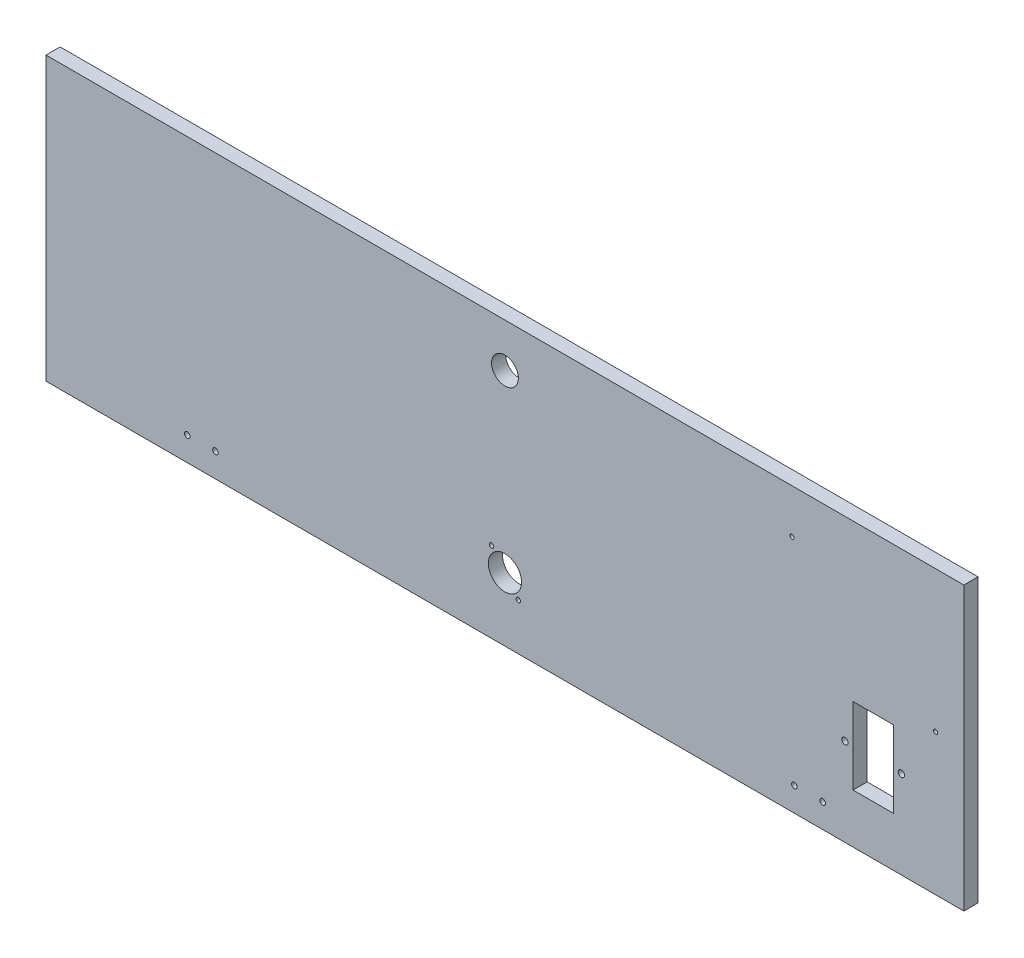
SolidWorks part; units mm, degrees
ref_plane "Plan de face" through (0, 0, 0) normal (0, 0, 1) x (1, 0, 0)
ref_plane "Plan de dessus" through (0, 0, 0) normal (0, 1, 0) x (1, 0, 0)
ref_plane "Plan de droite" through (0, 0, 0) normal (1, 0, 0) x (0, 0, -1)
sketch "Esquisse1" plane through (0, 0, 0) normal (0, 0, 1) x (1, 0, 0)
  line L1 (0, 0) -> (650, 0)
  line L2 (0, 0) -> (0, 200)
  line L3 (0, 200) -> (650, 200)
  line L4 (650, 0) -> (650, 200)
  dimension "D1" = 200
  dimension "D2" = 650
extrude "Boss.-Extru.1" add sketch "Esquisse1" along normal blind 10
sketch "Esquisse2" plane through (0, 0, 10) normal (0, 0, 1) x (1, 0, 0)
  line L4 (0, 200) -> (0, 0) construction
  line L5 (650, 0) -> (650, 200) construction
  line L6 (0, 0) -> (650, 0) construction
  circle A0 centre (100, 17) radius 2
  circle A1 centre (120, 17) radius 2
  circle A2 centre (530, 17) radius 2
  circle A3 centre (550, 17) radius 2
  dimension "D1" = 4
  dimension "D2" = 4
  dimension "D3" = 4
  dimension "D4" = 4
  dimension "D5" = 20
  dimension "D6" = 20
  dimension "D7" = 100
  dimension "D8" = 100
  dimension "D9" = 17
  dimension "D10" = 17
  dimension "D11" = 17
  dimension "D12" = 17
extrude "Enlèv. mat.-Extru.1" cut sketch "Esquisse2" against normal blind 10
sketch "Esquisse3" plane through (0, 0, 10) normal (0, 0, 1) x (1, 0, 0)
  line L0 (0, 0) -> (650, 0) construction
  line L1 (334.5004, 33.0006) -> (325, 45)
  line L2 (325, 45) -> (315.4996, 56.9994)
  line L3 (325, 45) -> (265.8175, 45)
  line L4 (325, 45) -> (364.3682, 45)
  line L5 (650, 0) -> (650, 200) construction
  line L6 (571.5, 35) -> (600, 35)
  line L7 (571.5, 35) -> (571.5, 89.3)
  line L8 (571.5, 89.3) -> (600, 89.3)
  line L9 (600, 35) -> (600, 89.3)
  circle A0 centre (325, 45) radius 11.75
  circle A1 centre (315.4996, 56.9994) radius 1.6
  circle A2 centre (334.5004, 33.0006) radius 1.6
  circle A3 centre (565.75, 62.15) radius 2.25
  circle A4 centre (605.75, 62.15) radius 2.25
  point P4 (325, 0)
  point P19 (585.75, 89.3)
  point P20 (571.5, 62.15)
  dimension "D1" = 23.5
  dimension "D4" = 3.2
  dimension "D5" = 3.2
  dimension "D14" = 4.5
  dimension "D15" = 4.5
  dimension "D2" = 0
  dimension "D3" = 45
  dimension "D6" = 30.61
  dimension "D7" = 15.305
  dimension "D8" = 51.63
  dimension "D9" = 180
  dimension "D10" = 51.63
  dimension "D11" = 15.305
  dimension "D12" = 28.5
  dimension "D13" = 54.3
  dimension "D16" = 40
  dimension "D17" = 20
  dimension "D18" = 0
  dimension "D19" = 35
  dimension "D20" = 50
  dimension "D21" = 20
extrude "Enlèv. mat.-Extru.2" cut sketch "Esquisse3" against normal blind 10 contours L3 A0 L1 | L4 A0 L2 | L1 A0 L4 | L2 A0 L3 | A1 | A2 | L6 L9 L8 L7 | A3 | A4 region at (314.1, 57.6764, 10) region at (322.2589, 39.3335, 10) region at (331.8154, 41.7031, 10) region at (335.1774, 34.4002, 10) region at (318.1846, 48.2969, 10) region at (327.7411, 50.6665, 10) region at (585.75, 62.15, 10)
sketch "Esquisse4" plane through (0, 0, 10) normal (0, 0, 1) x (1, 0, 0)
  line L0 (650, 200) -> (0, 200) construction
  circle A0 centre (325, 169) radius 9.5
  point P4 (325, 200)
  dimension "D1" = 19
  dimension "D3" = 31
  dimension "D2" = 0
extrude "Enlèv. mat.-Extru.3" cut sketch "Esquisse4" against normal blind 10
sketch "Esquisse5" plane through (0, 0, 0) normal (0, 0, 1) x (1, 0, 0)
  line L0 (650, 200) -> (0, 200) construction
  line L1 (650, 200) -> (0, 200) construction
  line L2 (0, 200) -> (0, 0) construction
  line L3 (650, 0) -> (650, 200) construction
  circle A0 centre (341, 169) radius 1
  circle A1 centre (309, 169) radius 1
  circle A2 centre (125, 193) radius 1
  circle A3 centre (105, 193) radius 1
  circle A4 centre (545, 193) radius 1
  circle A5 centre (525, 193) radius 1
  point P6 (325, 200)
  dimension "D2" = 2
  dimension "D3" = 2
  dimension "D7" = 2
  dimension "D8" = 2
  dimension "D9" = 2
  dimension "D10" = 2
  dimension "D1" = 32
  dimension "D4" = 16
  dimension "D5" = 31
  dimension "D6" = 31
  dimension "D11" = 20
  dimension "D12" = 7
  dimension "D13" = 7
  dimension "D14" = 105
  dimension "D15" = 7
  dimension "D16" = 7
  dimension "D17" = 20
  dimension "D18" = 105
extrude "Enlèv. mat.-Extru.4" cut sketch "Esquisse5" along normal blind 2
sketch "Esquisse6" plane through (0, 0, 0) normal (0, 0, -1) x (-1, 0, 0)
  line L0 (-650, 0) -> (-650, 200) construction
  line L1 (-650, 200) -> (0, 200) construction
  circle A0 centre (-528.25, 168.75) radius 1.5
  circle A1 centre (-630, 100) radius 1.5
  point P6 (-650, 100)
  point P9 (0, 0)
  point P11 (0, 0)
  dimension "D1" = 3
  dimension "D2" = 3
  dimension "D3" = 20
  dimension "D4" = 100
  dimension "D5" = 101.75
  dimension "D6" = 68.75
extrude "Enlèv. mat.-Extru.5" cut sketch "Esquisse6" against normal blind 10
